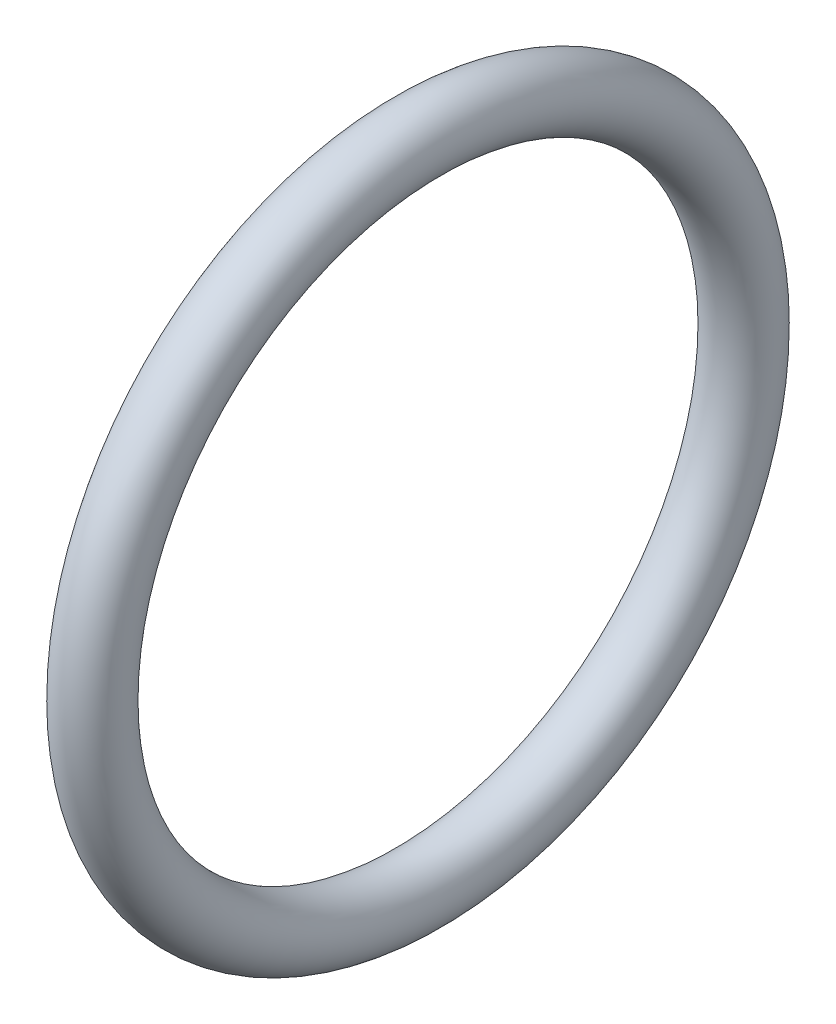
SolidWorks part; units mm, degrees
ref_plane "Plano frontal" through (0, 0, 0) normal (0, 0, 1) x (1, 0, 0)
ref_plane "Plano superior" through (0, 0, 0) normal (0, 1, 0) x (1, 0, 0)
ref_plane "Plano direito" through (0, 0, 0) normal (1, 0, 0) x (0, 0, -1)
sketch "Esboço1" plane through (0, 0, 0) normal (0, 0, 1) x (1, 0, 0)
  line L0 (0, 0) -> (0, 12.1) construction
  line L1 (0, 0) -> (21.9936, 0) construction
  circle A0 centre (0, 12.1) radius 1.2
  dimension "D1" = 2.4
  dimension "D2" = 12.1
revolve "Revolução1" add sketch "Esboço1" angle 360 about L1 other way angle 360
ref_axis "Eixo1" through (-2.3597, 0, 0) along (1, 0, 0)
